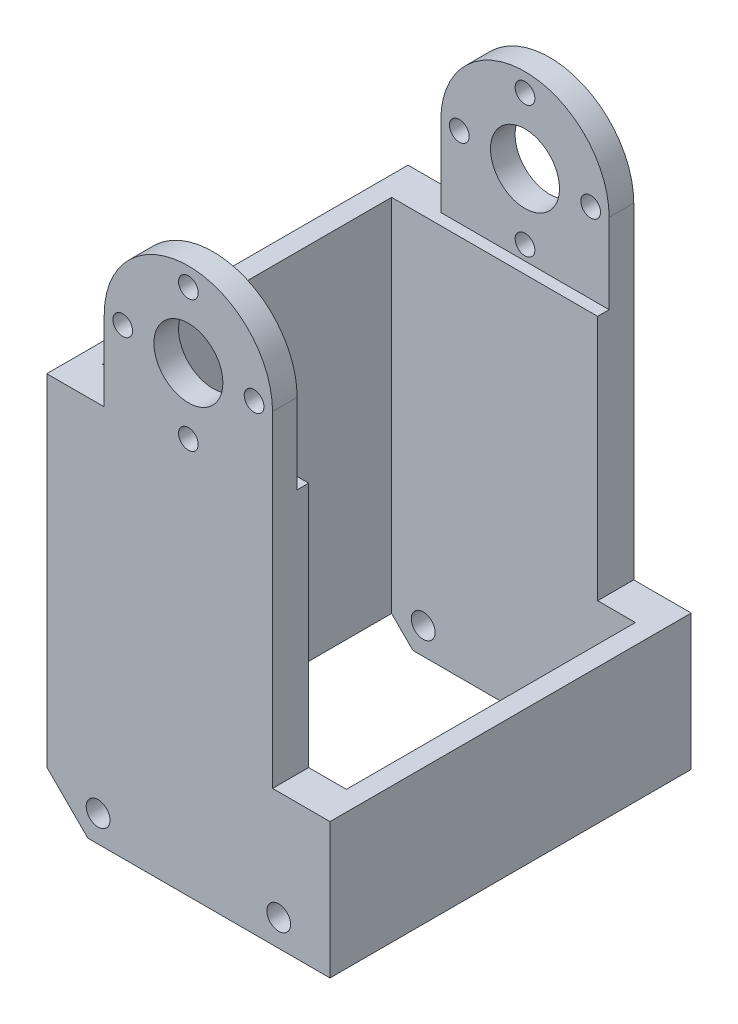
SolidWorks part; units mm, degrees
ref_plane "Front Plane" through (0, 0, 0) normal (0, 0, 1) x (1, 0, 0)
ref_plane "Top Plane" through (0, 0, 0) normal (0, 1, 0) x (1, 0, 0)
ref_plane "Right Plane" through (0, 0, 0) normal (1, 0, 0) x (0, 0, -1)
sketch "Sketch1" plane through (0, 0, 0) normal (0, 0, 1) x (1, 0, 0)
  line L0 (0, 0) -> (0, -100) construction
  line L1 (0, -100) -> (-70, -100) construction
  line L2 (-10.25, -60) -> (-70, -60) construction
  line L4 (-10.25, 0) -> (10.25, 0)
  line L5 (-10.25, 0) -> (-10.25, -60)
  line L7 (10.25, 0) -> (10.25, -60)
  line L8 (-10.25, 0) -> (10.25, 0)
  line L9 (-10.25, 0) -> (-10.25, -100)
  line L10 (-10.25, -100) -> (10.25, -100)
  line L11 (10.25, 0) -> (10.25, -100)
  circle A0 centre (0, 0) radius 10.25
  circle A1 centre (0, 0) radius 8
  circle A2 centre (0, 0) radius 4.2
  circle A3 centre (0, 8) radius 1.2
  circle A4 centre (8, 0) radius 1.2
  circle A5 centre (0, -8) radius 1.2
  circle A6 centre (-8, 0) radius 1.2
  point P16 (0, 0)
  dimension "D1" = 20.5
  dimension "D2" = 16
  dimension "D3" = 8.4
  dimension "D4" = 2.4
  dimension "D6" = 100
  dimension "D7" = 70
  dimension "D8" = 40
  dimension "D5" = 4
extrude "Boss-Extrude1" add sketch "Sketch1" along normal blind 22 and the other way blind 22 contours A0 L5 L7 | A6 L4 A0 A4 A1 A5 | A6 A1 A5 A4 L4 A2 | A6 L4 A2 A4 A1 A3 | A6 A1 A3 A4 L4 A0 region at (8.972, 1.0478, 0) region at (9.725, -0.2292, 0) region at (6.9906, -0.9364, 0) region at (5.5, 0.1769, 0) region at (0, -53.9967, 0)
sketch "Sketch2" plane through (-10.25, 0, 0) normal (-1, 0, 0) x (0, 0, 1)
  line L0 (22, 10.25) -> (-22, 10.25) construction
  line L1 (-19, 10.25) -> (19, 10.25)
  line L2 (-19, 10.25) -> (-19, -9.75)
  line L3 (-19, -9.75) -> (19, -9.75)
  line L4 (19, 10.25) -> (19, -9.75)
  line L5 (22, 0) -> (22, 10.25) construction
  line L6 (-22, 10.25) -> (-22, 0) construction
  dimension "D1" = 3
  dimension "D2" = 3
  dimension "D3" = 20
extrude "Cut-Extrude1" cut sketch "Sketch2" against normal through all
sketch "Sketch3" plane through (0, -9.75, 0) normal (0, 1, 0) x (1, 0, 0)
  line L1 (-10.25, 22) -> (-17.25, 22)
  line L2 (-10.25, 22) -> (-10.25, -22)
  line L3 (-10.25, -22) -> (-17.25, -22)
  line L4 (-17.25, 22) -> (-17.25, -22)
  line L5 (10.25, 22) -> (17.25, 22)
  line L6 (10.25, 22) -> (10.25, -22)
  line L7 (10.25, -22) -> (17.25, -22)
  line L8 (17.25, 22) -> (17.25, -22)
  dimension "D1" = 7
  dimension "D2" = 7
extrude "Boss-Extrude2" add sketch "Sketch3" against normal blind 65.5
sketch "Sketch23" plane through (0, 0, 22) normal (0, 0, 1) x (1, 0, 0)
  line L0 (10.25, -75.25) -> (17.25, -75.25) construction
  line L4 (10.25, -100) -> (-10.25, -100)
  line L5 (10.25, -100) -> (10.25, -75.25)
  line L6 (10.25, -75.25) -> (-10.25, -75.25)
  line L7 (-10.25, -100) -> (-10.25, -75.25)
  circle A0 centre (0, -85) radius 5
  circle A1 centre (0, 0) radius 4.2 construction
  circle A2 centre (0, -85) radius 8
  circle A3 centre (0, -77) radius 1.2
  circle A5 centre (8, -85) radius 1.2
  circle A6 centre (0, -93) radius 1.2
  circle A7 centre (-8, -85) radius 1.2
  circle A8 centre (0, -85) radius 10.25
  point P20 (0, -85)
  line M11 (-10.25, -100) -> (10.25, -100)
  line M12 (10.25, -100) -> (10.25, -75.25)
  dimension "D1" = 85
  dimension "D2" = 9.75
  dimension "D3" = 2.4
  dimension "D4" = 4
extrude "Cut-Extrude2" cut sketch "Sketch23" against normal through all contours A8 L7 M11 M12 | A2 A7 | A2 A7 | A2 A3 | A2 A3 | A2 A5 | A2 A5 | A2 A6 | A2 A6 | A0 region at (0, -96.1486, 22) region at (0, -85, 22) region at (7.4748, -85, 22) region at (8.4927, -85, 22) region at (0, -77.5252, 22) region at (0, -76.5073, 22) region at (0, -93.4927, 22) region at (0, -92.4748, 22) region at (-7.4748, -85, 22) region at (-8.4927, -85, 22)
sketch "Sketch24" plane through (0, -9.75, 0) normal (0, 1, 0) x (1, 0, 0)
  line L0 (17.25, -22) -> (17.25, 22) construction
  line L1 (-14.25, 17) -> (14.25, 17)
  line L2 (-14.25, 17) -> (-14.25, -17)
  line L3 (-14.25, -17) -> (14.25, -17)
  line L4 (14.25, 17) -> (14.25, -17)
  line L5 (-17.25, 22) -> (-17.25, -22) construction
  line L6 (10.25, 19) -> (-10.25, 19) construction
  line L7 (10.25, -19) -> (-10.25, -19) construction
  dimension "D1" = 3
  dimension "D2" = 3
  dimension "D3" = 2
  dimension "D4" = 2
extrude "Cut-Extrude3" cut sketch "Sketch24" against normal through all
sketch "Sketch26" plane through (0, 0, 22) normal (0, 0, 1) x (1, 0, 0)
  line L0 (-17.25, -75.25) -> (-17.25, -9.75) construction
  line L1 (14.25, -96.25) -> (-14.25, -96.25)
  line L2 (14.25, -96.25) -> (14.25, -49.75)
  line L3 (14.25, -49.75) -> (-14.25, -49.75)
  line L4 (-14.25, -96.25) -> (-14.25, -49.75)
  line L5 (17.25, -75.25) -> (17.25, -9.75) construction
  line L7 (-14.25, -49.75) -> (14.25, -49.75)
  line L8 (-14.25, -49.75) -> (-14.25, -56.5328)
  line L10 (14.25, -49.75) -> (14.25, -56.5328)
  line L11 (-14.25, -49.75) -> (14.25, -49.75)
  line L12 (-14.25, -49.75) -> (-14.25, -56.25)
  line L13 (-14.25, -56.25) -> (14.25, -56.25)
  line L14 (14.25, -49.75) -> (14.25, -56.25)
  line L15 (14.25, -56.25) -> (17.25, -56.25)
  line L16 (14.25, -56.25) -> (14.25, -75.25)
  line L17 (14.25, -75.25) -> (17.25, -75.25)
  line L18 (17.25, -56.25) -> (17.25, -75.25)
  line L19 (-17.25, -75.25) -> (-14.25, -75.25)
  line L20 (-17.25, -75.25) -> (-17.25, -56.25)
  line L21 (-17.25, -56.25) -> (-14.25, -56.25)
  line L22 (-14.25, -75.25) -> (-14.25, -56.25)
  arc A0 (-10.25, -85) -> (10.25, -85) centre (0, -85) ccw construction
  circle A1 centre (-11, -53) radius 1.45
  circle A2 centre (11, -53) radius 1.45
  circle M4 centre (0, -93) radius 1.2
  circle M5 centre (8, -85) radius 1.2
  circle M6 centre (0, -77) radius 1.2
  circle M7 centre (-8, -85) radius 1.2
  circle M8 centre (0, -85) radius 5
  line M14 (-10.25, -75.25) -> (-10.25, -85)
  arc M15 (-10.25, -85) -> (10.25, -85) centre (0, -85) ccw
  line M16 (10.25, -85) -> (10.25, -75.25)
  line M17 (10.25, -75.25) -> (17.25, -75.25)
  line M18 (17.25, -75.25) -> (17.25, -9.75)
  line M24 (-17.25, -9.75) -> (-17.25, -75.25)
  line M25 (-17.25, -75.25) -> (-10.25, -75.25)
  dimension "D4" = 2.9
  dimension "D5" = 3.25
  dimension "D6" = 3.25
  dimension "D1" = 3
  dimension "D2" = 3
  dimension "D3" = 11.25
  dimension "D8" = 3.25
  dimension "D9" = 46.5
  dimension "D7" = 2
extrude "Cut-Extrude6" cut sketch "Sketch26" against normal through all contours L13 L4 L2 M25 M14 M15 M16 M17 M5 M7 M8 M6 M4 | L21 L4 M24 M25 | L15 L2 M17 M18 | A1 | A2 region at (0, -71.8107, 22) region at (15.75, -65.75, 22) region at (-15.75, -65.75, 22) region at (-11, -53, 22) region at (11, -53, 22)
sketch "Sketch27" plane through (0, -56.25, 0) normal (0, -1, 0) x (1, 0, 0)
  line L0 (-14.25, 17) -> (14.25, 17) construction
  line L1 (-14.85, -17.6) -> (14.85, -17.6)
  line L2 (-14.85, -17.6) -> (-14.85, 17.6)
  line L3 (-14.85, 17.6) -> (14.85, 17.6)
  line L4 (14.85, -17.6) -> (14.85, 17.6)
  line L5 (-14.85, -17.6) -> (14.85, 17.6) construction
  line L6 (-14.85, 17.6) -> (14.85, -17.6) construction
  line L7 (14.25, 17) -> (14.25, -17) construction
  point P0 (0, 0)
  dimension "D1" = 0.6
  dimension "D2" = 0.6
extrude "Cut-Extrude8" cut sketch "Sketch27" against normal through all
sketch "Sketch29" plane through (0, 0, -22) normal (0, 0, -1) x (-1, 0, 0)
  line L1 (-17.25, -9.75) -> (-10.25, -9.75)
  line L2 (-17.25, -9.75) -> (-17.25, -39.75)
  line L3 (-17.25, -39.75) -> (-10.25, -39.75)
  line L4 (-10.25, -9.75) -> (-10.25, -39.75)
  dimension "D1" = 30
extrude "Cut-Extrude10" cut sketch "Sketch29" against normal through all
chamfer "Chamfer2" distance 5 angle 45 1 edges at (-17.25, -56.25, 0)
